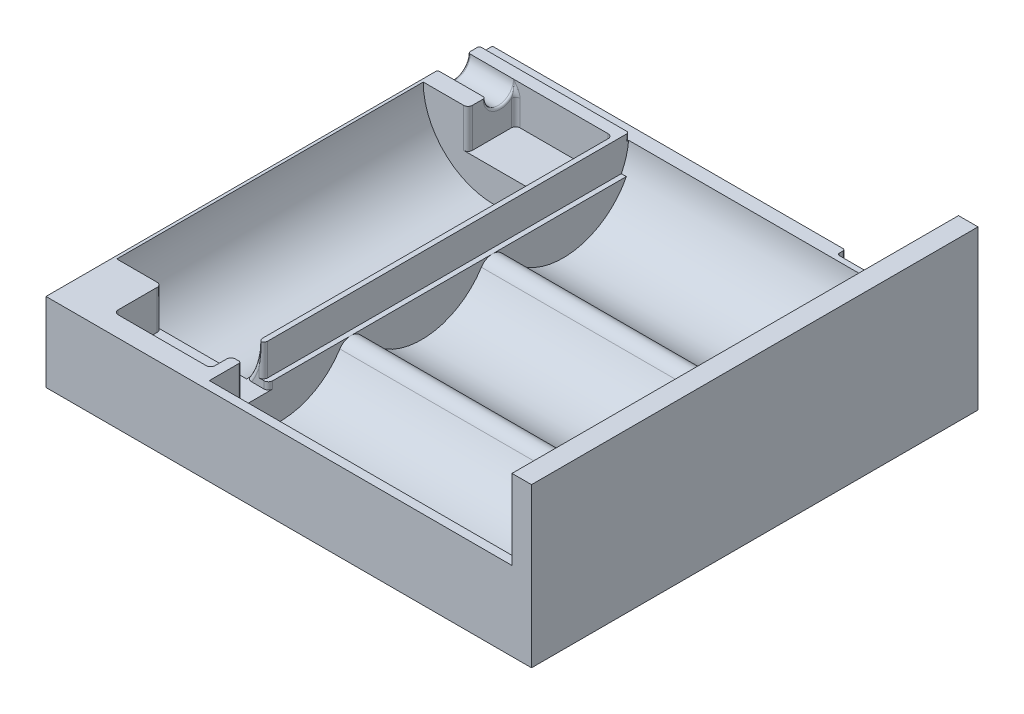
SolidWorks part; units mm, degrees
ref_plane "Front Plane" through (0, 0, 0) normal (0, 0, 1) x (1, 0, 0)
ref_plane "Top Plane" through (0, 0, 0) normal (0, 1, 0) x (1, 0, 0)
ref_plane "Right Plane" through (0, 0, 0) normal (1, 0, 0) x (0, 0, -1)
sketch "Sketch1" plane through (0, 0, 0) normal (0, 1, 0) x (1, 0, 0)
  line L1 (-56, 52) -> (56, 52)
  line L2 (-56, 52) -> (-56, -52)
  line L3 (-56, -52) -> (56, -52)
  line L4 (56, 52) -> (56, -52)
  line L5 (-56, 52) -> (56, -52) construction
  line L6 (-56, -52) -> (56, 52) construction
  point P0 (0, 0)
  dimension "D1" = 104
  dimension "D2" = 112
extrude "Boss-Extrude1" add sketch "Sketch1" along normal blind 18.2
ref_plane "Plane1" through (51.5, 0, 0) normal (1, 0, 0) x (0, 0, -1)
sketch "Sketch2" plane through (51.5, 0, 0) normal (1, 0, 0) x (0, 0, -1)
  line L0 (-52, 18.2) -> (52, 18.2) construction
  line L1 (0, 0) -> (0, -18.713) construction
  circle A0 centre (0, 18.2) radius 16.325
  circle A1 centre (32.65, 18.2) radius 16.325
  circle A2 centre (-32.65, 18.2) radius 16.325
  dimension "D1" = 32.65
  dimension "D2" = 32.65
extrude "Cut-Extrude1" cut sketch "Sketch2" against normal blind 73 contours A0 | A2 | A1 region at (51.5, 18.2, 0) region at (51.5, 18.2, 32.65) region at (51.5, 18.2, -32.65)
fillet "Fillet1" radius 3 2 edges at (15, 18.2, -16.325) (15, 18.2, 16.325)
sketch "Sketch3" plane through (0, 0, 0) normal (0, 0, 1) x (1, 0, 0)
  line L0 (56, 18.2) -> (-56, 18.2) construction
  circle A0 centre (-39, 18.2) radius 16.325
  dimension "D1" = 32.65
  dimension "D2" = 39
extrude "Cut-Extrude2" cut sketch "Sketch3" against normal blind 35.35 and the other way blind 35.35
sketch "Sketch4" plane through (0, 0, -35.35) normal (0, 0, 1) x (1, 0, 0)
  line L0 (-45, 18.2) -> (-45, 9.2)
  line L1 (-55.325, 18.2) -> (-22.675, 18.2) construction
  line L2 (-45, 18.2) -> (-22.675, 18.2)
  line L3 (-45, 9.2) -> (-25.38, 9.2)
  arc A0 (-55.325, 18.2) -> (-22.675, 18.2) centre (-39, 18.2) ccw construction
  arc A1 (-25.38, 9.2) -> (-22.675, 18.2) centre (-39, 18.2) ccw
  dimension "D1" = 9
  dimension "D2" = 6
extrude "Cut-Extrude3" cut sketch "Sketch4" against normal blind 11
mirror "Mirror1" about plane through (0, 0, 0) normal (0, 0, 1) of "Cut-Extrude3"
sketch "Sketch5" plane through (-21.5, 0, 0) normal (1, 0, 0) x (0, 0, -1)
  line L0 (-41.65, 18.2) -> (-41.65, 9.2)
  line L1 (-48.975, 18.2) -> (-16.325, 18.2) construction
  line L2 (-41.65, 9.2) -> (-19.03, 9.2)
  line L3 (-46.35, 9.2) -> (-35.35, 9.2) construction
  line L4 (-41.65, 18.2) -> (-16.325, 18.2)
  line L5 (-16.325, 18.2) -> (16.325, 18.2) construction
  arc A0 (-48.975, 18.2) -> (-18.8593, 9.4638) centre (-32.65, 18.2) ccw construction
  arc A1 (-19.03, 9.2) -> (-18.8593, 9.4638) centre (-32.65, 18.2) ccw
  arc A2 (-18.8593, 9.4638) -> (-16.325, 18.2) centre (-32.65, 18.2) ccw
  dimension "D1" = 9
extrude "Cut-Extrude4" cut sketch "Sketch5" against normal blind 10
sketch "Sketch6" plane through (-45, 0, 0) normal (1, 0, 0) x (0, 0, -1)
  line L2 (46.35, 18.2) -> (46.35, 9.2) construction
  line L3 (46.35, 18.2) -> (35.35, 18.2) construction
  circle A0 centre (42.85, 18.2) radius 3.5
  dimension "D1" = 7
extrude "Cut-Extrude6" cut sketch "Sketch6" against normal through all and the other way blind 1
sketch "Sketch7" plane through (-21.5, 0, 0) normal (1, 0, 0) x (0, 0, -1)
  line L0 (47.231, 10.8583) -> (-16.325, 10.8583)
  arc A0 (18.8593, 9.4638) -> (48.975, 18.2) centre (32.65, 18.2) ccw construction
  arc A1 (18.8593, 9.4638) -> (13.7907, 9.4638) centre (16.325, 7.8583) ccw construction
  arc A2 (-13.7907, 9.4638) -> (13.7907, 9.4638) centre (0, 18.2) ccw construction
  arc A3 (18.8593, 9.4638) -> (47.231, 10.8583) centre (32.65, 18.2) ccw
  arc A4 (18.8593, 9.4638) -> (13.7907, 9.4638) centre (16.325, 7.8583) ccw
  arc A5 (-13.7907, 9.4638) -> (13.7907, 9.4638) centre (0, 18.2) ccw
  arc A6 (-13.7907, 9.4638) -> (-18.8593, 9.4638) centre (-16.325, 7.8583) ccw construction
  arc A7 (-13.7907, 9.4638) -> (-16.325, 10.8583) centre (-16.325, 7.8583) ccw
  arc M4 (-18.8593, 9.4638) -> (-13.7907, 9.4638) centre (-16.325, 7.8583) cw
  arc M5 (-13.7907, 9.4638) -> (13.7907, 9.4638) centre (0, 18.2) ccw
  arc M6 (13.7907, 9.4638) -> (18.8593, 9.4638) centre (16.325, 7.8583) cw
  arc M7 (18.8593, 9.4638) -> (48.975, 18.2) centre (32.65, 18.2) ccw
extrude "Boss-Extrude2" add sketch "Sketch7" along normal blind 1.15 contours L0 M7 M6 | L0 M6 M4 M5 region at (-21.5, 7.1725, -32.613) region at (-21.5, 7.1809, 0)
ref_plane "Plane2" through (15, 0, 0) normal (1, 0, 0) x (0, 0, -1)
mirror "Mirror2" about plane through (15, 0, 0) normal (1, 0, 0) of "Boss-Extrude2"
sketch "Sketch8" plane through (-21.5, 0, 0) normal (1, 0, 0) x (0, 0, -1)
  line L3 (-19.03, 9.2) -> (-41.65, 9.2)
  line L4 (-41.65, 9.2) -> (-41.65, 18.2)
  line L5 (-41.65, 9.2) -> (-41.65, 18.2)
  line L6 (-19.03, 9.2) -> (-41.65, 9.2)
  line L9 (-41.65, 18.2) -> (-48.975, 18.2)
  line L20 (-41.65, 18.2) -> (-48.975, 18.2)
  arc A1 (-48.975, 18.2) -> (-19.03, 9.2) centre (-32.65, 18.2) ccw
  arc A2 (-48.975, 18.2) -> (-19.03, 9.2) centre (-32.65, 18.2) ccw
  dimension "D1" = 0
extrude "Boss-Extrude3" add sketch "Sketch8" along normal up to surface (1.15 mm away) up to face at (-20.35, 8.4267, 0)
mirror "Mirror3" about plane through (15, 0, 0) normal (1, 0, 0) of "Boss-Extrude3"
sketch "Sketch10" plane through (0, 18.2, 0) normal (0, 1, 0) x (1, 0, 0)
  line L0 (51.5, -20.13) -> (51.5, 20.13) construction
  line L1 (50.35, 47.231) -> (51.5, 47.231)
  line L2 (50.35, 47.231) -> (50.35, 50.1549)
  line L3 (50.35, 56.7433) -> (51.5, 56.7433)
  line L4 (51.5, 47.231) -> (51.5, 56.7433)
  line L5 (56, 52) -> (-56, 52) construction
  line L6 (50.35, 50.1549) -> (25.35, 50.1549)
  line L8 (50.35, 52) -> (25.35, 52)
  line L9 (25.35, 50.1549) -> (25.35, 52)
  line L10 (50.35, 52) -> (50.35, 56.7433)
  dimension "D1" = 2.9239
  dimension "D2" = 25
extrude "Cut-Extrude9" cut sketch "Sketch10" against normal blind 6
sketch "Sketch11" plane through (0, 18.2, 0) normal (0, 1, 0) x (1, 0, 0)
  line L6 (51.5, 52) -> (56, 52)
  line L7 (51.5, 52) -> (51.5, -52)
  line L8 (51.5, -52) -> (56, -52)
  line L9 (56, 52) -> (56, -52)
  point P4 (0, 0)
extrude "Boss-Extrude4" add sketch "Sketch11" along normal blind 18.4
sketch "Sketch13" plane through (-56, 0, 0) normal (-1, 0, 0) x (0, 0, 1)
  line L1 (-52, 18.2) -> (-48.975, 18.2)
  line L2 (-52, 18.2) -> (-52, 16.7)
  line L3 (-52, 16.7) -> (-48.9059, 16.7)
  line L7 (-47.231, 10.8583) -> (16.325, 10.8583)
  line L8 (-16.325, 18.2) -> (-48.975, 18.2)
  line L9 (16.325, 18.2) -> (-16.325, 18.2)
  arc A3 (18.8593, 9.4638) -> (16.325, 10.8583) centre (16.325, 7.8583) ccw
  arc A4 (-48.975, 18.2) -> (-47.231, 10.8583) centre (-32.65, 18.2) ccw
  arc A5 (16.325, 18.2) -> (18.8593, 9.4638) centre (32.65, 18.2) ccw
  arc A7 (-48.975, 18.2) -> (-48.9059, 16.7) centre (-32.65, 18.2) ccw
  dimension "D2" = 1.5
  dimension "D1" = 0
sketch "Sketch15" plane through (0, 0, 52) normal (0, 0, 1) x (1, 0, 0)
  line L6 (-56, 0) -> (56, 0)
  line L7 (56, 0) -> (56, 36.6)
  line L8 (56, 36.6) -> (51.5, 36.6)
  line L10 (51.5, 18.2) -> (-56, 18.2)
  line L11 (-56, 18.2) -> (-56, 0)
  line L12 (-56, 0) -> (56, 0)
  line L13 (56, 0) -> (56, 36.6)
  line L16 (51.5, 18.2) -> (-56, 18.2)
  line L17 (-56, 18.2) -> (-56, 0)
  line L18 (56, 36.6) -> (51.5, 36.6)
  line L20 (51.5, 36.6) -> (51.5, 18.2)
  line L21 (51.5, 36.6) -> (51.5, 18.2)
  dimension "D1" = 0
extrude "Cut-Extrude12" cut sketch "Sketch15" against normal blind 1
extrude "Cut-Extrude13" cut sketch "Sketch13" against normal up to surface (107.5 mm away) up to face at (51.5, 16.7181, 3.6922)
ref_plane "Plane3" through (0, 0, 35.35) normal (0, 0, -1) x (-1, 0, 0)
sketch "Sketch17" plane through (0, 0, 35.35) normal (0, 0, -1) x (-1, 0, 0)
  line L3 (22.675, 18.2) -> (20.35, 18.2)
  line L4 (20.35, 18.2) -> (20.35, 9.2)
  line L5 (20.35, 9.2) -> (25.38, 9.2)
  line L6 (22.675, 18.2) -> (20.35, 18.2)
  line L7 (20.35, 18.2) -> (20.35, 9.2)
  line L8 (20.35, 9.2) -> (25.38, 9.2)
  arc A1 (22.675, 18.2) -> (25.38, 9.2) centre (39, 18.2) ccw
  arc A2 (22.675, 18.2) -> (25.38, 9.2) centre (39, 18.2) ccw
  dimension "D1" = 0
extrude "Boss-Extrude5" add sketch "Sketch17" along normal blind 19.3 contours A2 L8 L7 L6
fillet "Fillet9" radius 0.5 11 edges at (25.35, 14.45, -52) (25.35, 14.45, -50.1549) (-20.35, 13.7, 41.65) (-56, 17.4492, -48.9577) (-21.5, 17.4492, -48.9577) (50.35, 13.7, 41.65) (51.5, 13.7, 41.65) (50.35, 14.4118, -48.5294) (50.35, 14.45, -50.1549) (-45, 14.7, -42.85) (-56, 14.7, -42.85)
sketch "Sketch18" plane through (0, 0, 16.05) normal (0, 0, -1) x (-1, 0, 0)
  line L4 (20.35, 10.8583) -> (21.5, 10.8583)
  line L5 (21.5, 10.8583) -> (21.5, 18.2)
  line L6 (21.5, 18.2) -> (20.35, 18.2)
  line L7 (20.35, 18.2) -> (20.35, 10.8583)
  line L8 (20.35, 10.8583) -> (21.5, 10.8583)
  line L9 (21.5, 10.8583) -> (21.5, 18.2)
  line L10 (21.5, 18.2) -> (20.35, 18.2)
  line L11 (20.35, 18.2) -> (20.35, 10.8583)
  dimension "D1" = 0
extrude "Cut-Extrude14" cut sketch "Sketch18" against normal blind 22
fillet "Fillet12" radius 1 11 edges at (-23.3659, 13.5011, 41.65) (-23.3659, 13.5011, 46.35) (-45, 13.7, 46.35) (-45, 13.7, 35.35) (-23.3659, 13.5011, -46.35) (-45, 13.7, -35.35) (-45, 12.7318, -46.35) (-45.1487, 17.185, -46.35) (-20.35, 10.0292, 35.35) (-23.3659, 13.5011, 35.35) (-21.5, 14.5292, 35.35)
